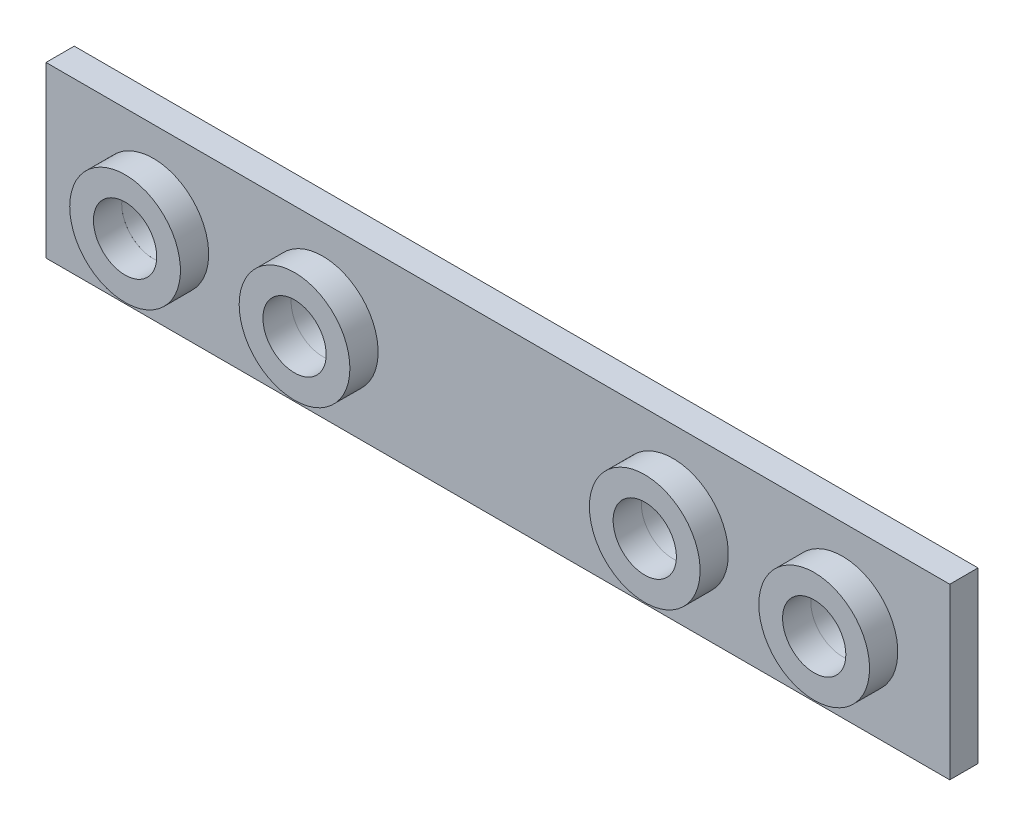
SolidWorks part; units mm, degrees
ref_plane "Front Plane" through (0, 0, 0) normal (0, 0, 1) x (1, 0, 0)
ref_plane "Top Plane" through (0, 0, 0) normal (0, 1, 0) x (1, 0, 0)
ref_plane "Right Plane" through (0, 0, 0) normal (1, 0, 0) x (0, 0, -1)
sketch "Sketch1" plane through (0, 0, 0) normal (0, 0, 1) x (1, 0, 0)
  line L0 (-23, 0) -> (23, 0) construction
  line L1 (0, 22.8395) -> (0, -24.8721) construction
  line L2 (-23, 12.8907) -> (-23, -21.4488) construction
  circle A0 centre (-15.5, 0) radius 2.8
  circle A1 centre (-30.5, 0) radius 2.8
  circle A2 centre (30.5, 0) radius 2.8
  circle A3 centre (15.5, 0) radius 2.8
  circle A4 centre (-15.5, 0) radius 4.9
  circle A5 centre (-30.5, 0) radius 4.9
  circle A6 centre (15.5, 0) radius 4.9
  circle A7 centre (30.5, 0) radius 4.9
  point P3 (0, 0)
  dimension "D2" = 5.6
  dimension "D4" = 9.8
  dimension "D1" = 46
  dimension "D3" = 7.5
extrude "Boss-Extrude1" add sketch "Sketch1" along normal blind 5
sketch "Sketch3" plane through (0, 0, 0) normal (0, 0, 1) x (1, 0, 0)
  line L1 (-40, -7.5) -> (40, -7.5)
  line L2 (-40, -7.5) -> (-40, 7.5)
  line L3 (-40, 7.5) -> (40, 7.5)
  line L4 (40, -7.5) -> (40, 7.5)
  line L5 (-40, -7.5) -> (40, 7.5) construction
  line L6 (-40, 7.5) -> (40, -7.5) construction
  point P0 (0, 0)
  dimension "D1" = 80
  dimension "D2" = 15
extrude "Boss-Extrude2" add sketch "Sketch3" along normal blind 2.5
sketch "Sketch4" plane through (0, 0, 5) normal (0, 0, 1) x (1, 0, 0)
  circle A0 centre (-30.5, 0) radius 2.8
  circle A1 centre (-15.5, 0) radius 2.8
  circle A2 centre (15.5, 0) radius 2.8
  circle A3 centre (30.5, 0) radius 2.8
  circle A4 centre (-30.5, 0) radius 2.8 construction
  circle A5 centre (-15.5, 0) radius 2.8 construction
  circle A6 centre (15.5, 0) radius 2.8 construction
  circle A7 centre (30.5, 0) radius 2.8 construction
extrude "Cut-Extrude1" cut sketch "Sketch4" against normal through all
split "Split1" bodies to split 106 resulting bodies 107 108 109 110 111 split by face at (25.6, 0, 2.5)
